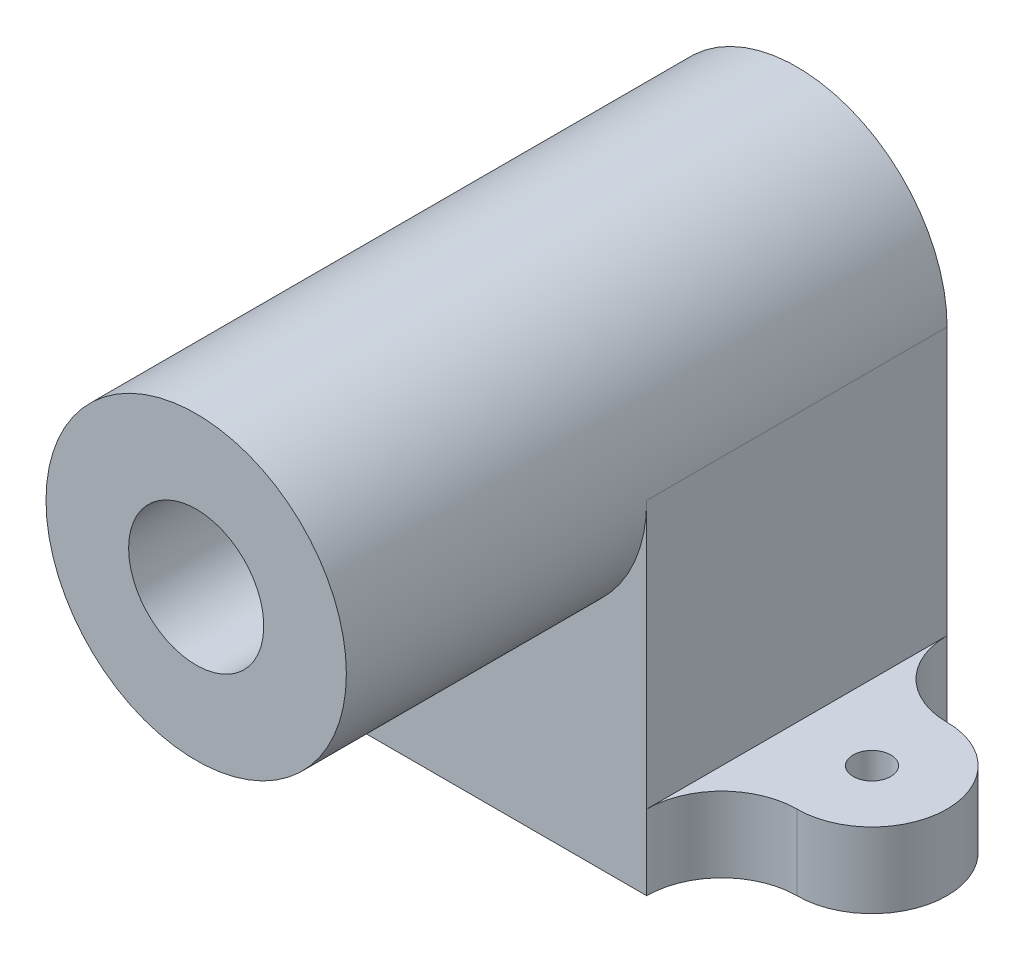
SolidWorks part; units mm, degrees
ref_plane "Front Plane" through (0, 0, 0) normal (0, 0, 1) x (1, 0, 0)
ref_plane "Top Plane" through (0, 0, 0) normal (0, 1, 0) x (1, 0, 0)
ref_plane "Right Plane" through (0, 0, 0) normal (1, 0, 0) x (0, 0, -1)
sketch "Sketch1" plane through (0, 0, 0) normal (0, 1, 0) x (1, 0, 0)
  line L0 (15, 0) -> (-15, 0) construction
  line L1 (-10, -10) -> (10, -10)
  line L2 (-10, -10) -> (-10, -5)
  line L3 (-10, 10) -> (10, 10)
  line L4 (10, -10) -> (10, -5)
  line L5 (-10, -10) -> (10, 10) construction
  line L6 (-10, 10) -> (10, -10) construction
  line L7 (0, -55) -> (0, 55) construction
  line L8 (-15, 5) -> (-10, 5)
  line L9 (-10, 5) -> (-10, 10)
  line L10 (15, -5) -> (10, -5)
  line L11 (10, 5) -> (10, 10)
  line L12 (10, 5) -> (15, 5)
  line L14 (-10, -5) -> (-15, -5)
  circle A0 centre (-15, 0) radius 1.25
  arc A1 (-15, 5) -> (-15, -5) centre (-15, 0) ccw
  arc A2 (15, 5) -> (15, -5) centre (15, 0) cw
  circle A3 centre (15, 0) radius 1.25
  point P0 (0, 0)
  point P9 (0, 0)
  dimension "D1" = 10
  dimension "D5" = 2.5
  dimension "D2" = 20
  dimension "D3" = 20
  dimension "D4" = 30
extrude "Boss-Extrude1" add sketch "Sketch1" along normal blind 5
ref_plane "Plane1" through (0, 22.8, 0) normal (0, -1, 0) x (-1, 0, 0)
sketch "Sketch2" plane through (0, 5, 0) normal (0, 1, 0) x (1, 0, 0)
  line L1 (-10, -10) -> (10, -10)
  line L2 (-10, -10) -> (-10, 10)
  line L3 (-10, 10) -> (10, 10)
  line L4 (10, -10) -> (10, 10)
  line L5 (-10, -10) -> (10, 10) construction
  line L6 (-10, 10) -> (10, -10) construction
  point P0 (0, 0)
extrude "Boss-Extrude2" add sketch "Sketch2" along normal up to surface (17.8 mm away) up to plane "Plane1"
sketch "Sketch3" plane through (0, 0, -10) normal (0, 0, -1) x (-1, 0, 0)
  line L0 (10, 22.8) -> (-10, 22.8) construction
  circle A1 centre (0, 22.8) radius 4.5
  circle A2 centre (0, 22.8) radius 10
  line M4 (10, 22.8) -> (-10, 22.8)
  dimension "D1" = 9
extrude "Boss-Extrude3" add sketch "Sketch3" against normal blind 40 contours A2 A1 M4 | A1 M4 | A2 A1 M4 | A1 M4 region at (0, 24.7099, -10) region at (0, 17.9632, -10) region at (0, 27.6368, -10) region at (0, 20.8901, -10)
extrude "Cut-Extrude1" cut sketch "Sketch3<3>" against normal through all contours A1 M4 | A1 M4 region at (0, 24.7099, -10) region at (0, 20.8901, -10)
sketch "Sketch3<3>" plane through (0, 0, -10) normal (0, 0, -1) x (-1, 0, 0) same geometry as "Sketch3"
fillet "Fillet1" radius 5 4 edges at (10, 2.5, -5) (10, 2.5, 5) (-10, 2.5, 5) (-10, 2.5, -5)
chamfer "Chamfer2" distance 3 angle 45 1 edges at (-4.5, 22.8, -10)
